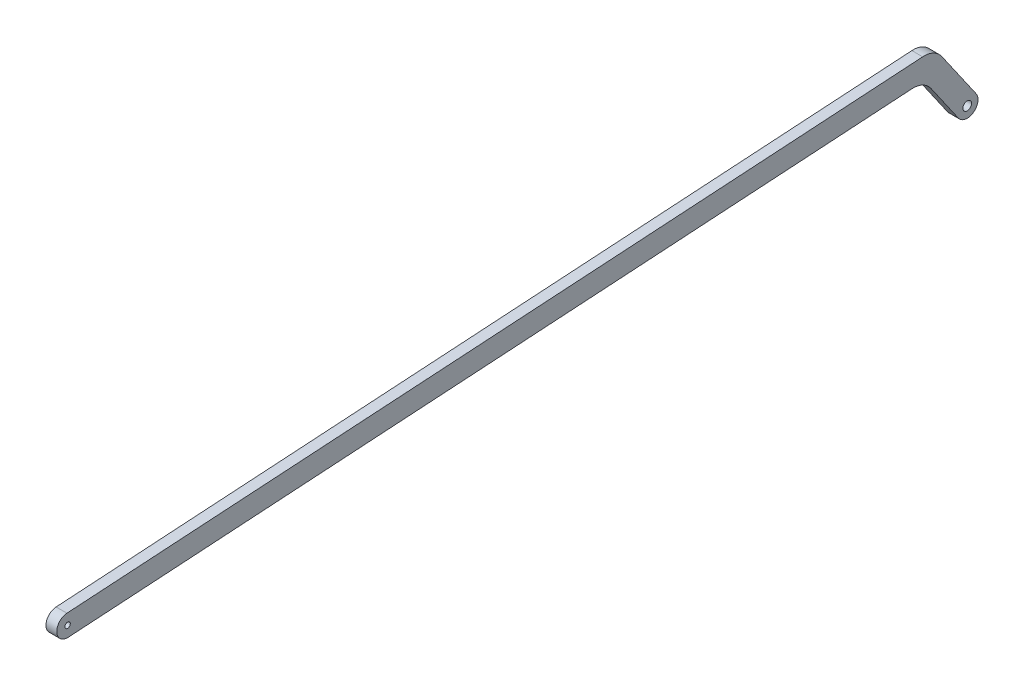
SolidWorks part; units mm, degrees
material "6061-T6 (SS)"
ref_plane "Front Plane" through (0, 0, 0) normal (0, 0, 1) x (1, 0, 0)
ref_plane "Top Plane" through (0, 0, 0) normal (0, 1, 0) x (1, 0, 0)
ref_plane "Right Plane" through (0, 0, 0) normal (1, 0, 0) x (0, 0, -1)
sketch "Sketch3" plane through (0, 0, 0) normal (1, 0, 0) x (0, 0, -1)
  line L6 (-0.3996, 6.3374) -> (510.0999, 38.525)
  line L7 (510.0999, 38.525) -> (534.3718, 3.6257)
  line L8 (0, 0) -> (529.1587, 0) construction
  line L9 (0.3996, -6.3374) -> (503.7587, 25.4)
  line L10 (503.7587, 25.4) -> (523.9455, -3.6257)
  circle A0 centre (0, 0) radius 1.6
  circle A1 centre (529.1587, 0) radius 2.5527
  circle A2 centre (0, 0) radius 6.35
  circle A3 centre (529.1587, 0) radius 6.35
  point P8 (0, 0)
  dimension "D5" = 529.1587
  dimension "D8" = 12.7
  dimension "D11" = 5.1054
  dimension "D3" = 3.2
  dimension "D4" = 12.7
  dimension "D2" = 25.4
  dimension "D6" = 25.4
extrude "Boss-Extrude1" add sketch "Sketch3" along normal blind 6.35 contours A0 A2 | L8 A2 L9 | A2 L8 L9 L10 A3 L7 L6 | L8 L10 A3 | A3 A1 region at (0, 17.0993, -282.8141) region at (0, 4.4983, -4.2236) region at (0, -2.058, -37.0239) region at (0, 1.8461, -535.0464) region at (0, -0.9413, -522.5003)
fillet "Fillet1" radius 12.7 2 edges at (3.175, 38.525, -510.0999) (3.175, 25.4, -503.7587)
